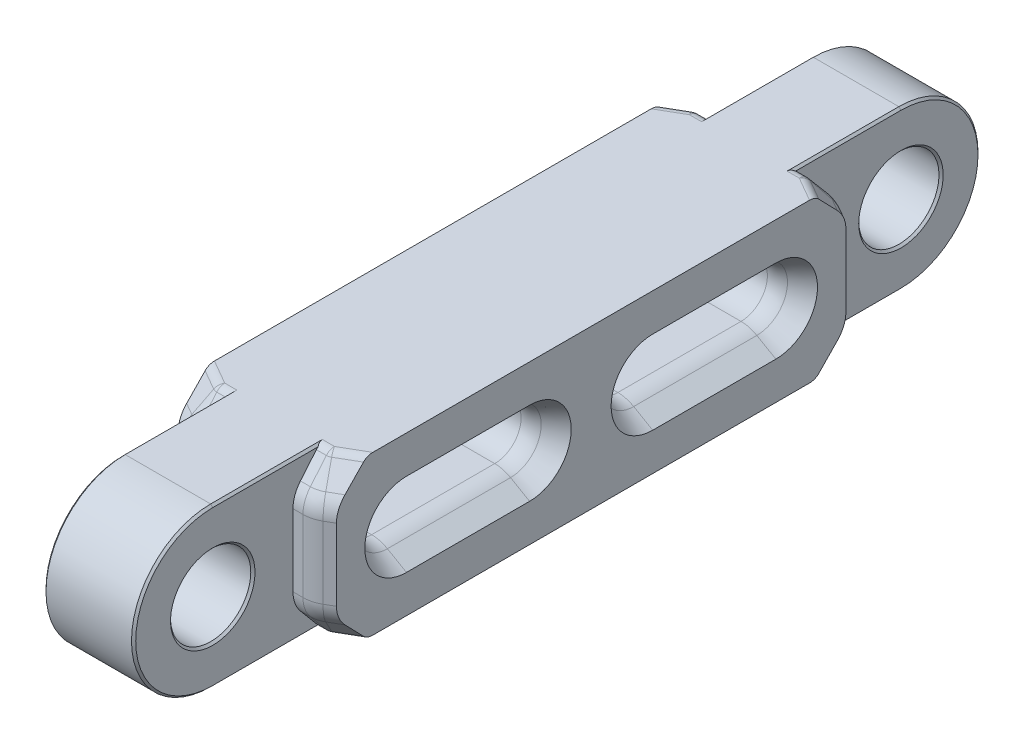
SolidWorks part; units mm, degrees
ref_plane "Front Plane" through (0, 0, 0) normal (1, 0, 0) x (0, 1, 0)
ref_plane "Top Plane" through (0, 0, 0) normal (0, 0, 1) x (0, 1, 0)
ref_plane "Right Plane" through (0, 0, 0) normal (0, 1, 0) x (-1, 0, 0)
sketch "Sketch1" plane through (0, 0, 0) normal (1, 0, 0) x (0, 1, 0)
  line L0 (-15, 0) -> (-15, -130.4)
  line L1 (-15, -65.2) -> (15, -65.2) construction
  line L2 (15, -130.4) -> (15, 0)
  line L3 (-5, -30.2) -> (-5, -53.5333)
  line L4 (-15, -115.2) -> (15, -115.2)
  line L6 (-15, -15.2) -> (15, -15.2)
  line L7 (0, 15) -> (0, -65.2)
  circle A0 centre (0, 0) radius 7.6
  circle A1 centre (0, 0) radius 15
  circle A26 centre (0, -130.4) radius 15
  circle A27 centre (0, -130.4) radius 7.6
  circle A28 centre (0, -53.5333) radius 5
  circle A29 centre (0, -30.2) radius 5
  point P16 (-5, -53.5333)
  point P17 (0, -58.5333)
  point P20 (0, -25.2)
  dimension "D1" = 30
  dimension "D2" = 15.2
  dimension "D3" = 15.2
  dimension "D4" = 100
  dimension "D5" = 10
  dimension "D6" = 6.6667
  dimension "D7" = 10
extrude "Boss-Extrude1" add sketch "Sketch1" along normal blind 8.5 contours L7 A1 A0 | A1 L0 L6 L7 | L0 L1 L7 L6 region at (0, -11.4068, -11.8513) region at (0, -10.3694, 10.3694) region at (0, -8.8374, -39.7625)
extrude "Boss-Extrude2" add sketch "Sketch1<4>" along normal blind 15 contours L0 L1 L7 L6 region at (0, -8.8374, -39.7625)
sketch "Sketch1<4>" plane through (0, 0, 0) normal (1, 0, 0) x (0, 1, 0) same geometry as "Sketch1"
chamfer "Chamfer8" distance 3 angle 30 1 edges at (15, -7.5, -15.2) first distance on face at (11.75, -7.5, -15.2)
fillet "Fillet6" radius 6 1 edges at (12, -7.5, -15.2)
chamfer "Chamfer9" distance 6 angle 40 3 edges at (14.1962, -15, -16.4679) (11.9452, -15, -15.4044) (9.4462, -15, -15.2) first distance on face at (14.1962, -7.5, -16.4679) first distance on face at (11.9188, -7.5, -15.5032) first distance on face at (9.4462, -7.5, -15.2)
fillet "Fillet7" radius 6 3 edges at (14.1962, -9, -16.4679) (11.9452, -9, -15.4044) (9.4462, -9, -15.2)
chamfer "Chamfer10" distance 5 angle 30 3 edges at (15, -3.5355, -57.0689) (15, -5, -41.8667) (15, -3.5355, -26.6645) first distance on face at (7.5, -3.0178, -56.5511) first distance on face at (7.5, -5, -41.8667) first distance on face at (7.5, -3.0178, -27.1822)
fillet "Fillet8" radius 6 3 edges at (10, -3.5355, -57.0689) (10, -5, -41.8667) (10, -3.5355, -26.6645)
fillet "Fillet9" radius 2 3 edges at (9.4462, -15, -20.2346) (10.6422, -15, -20.2675) (12.9375, -15, -21.5547)
chamfer "Chamfer11" distance 0.4 angle 45 3 edges at (8.5, -7.6, 0) (8.5, -15, -10.5836) (8.5, -10.6066, 10.6066)
mirror "Mirror1" about plane through (8.5, 0, 0) normal (0, 1, 0) of bodies 102
mirror "Mirror2" about plane through (8.5, 0, -65.2) normal (0, 0, 1) of bodies 108
mirror "Mirror3" about plane through (0, 0, 0) normal (1, 0, 0) of bodies 109
equation "\"D6@Sketch1\"=\"D5@Sketch1\"*2/3"
equation "\"D7@Sketch1\"=\"D5@Sketch1\""
